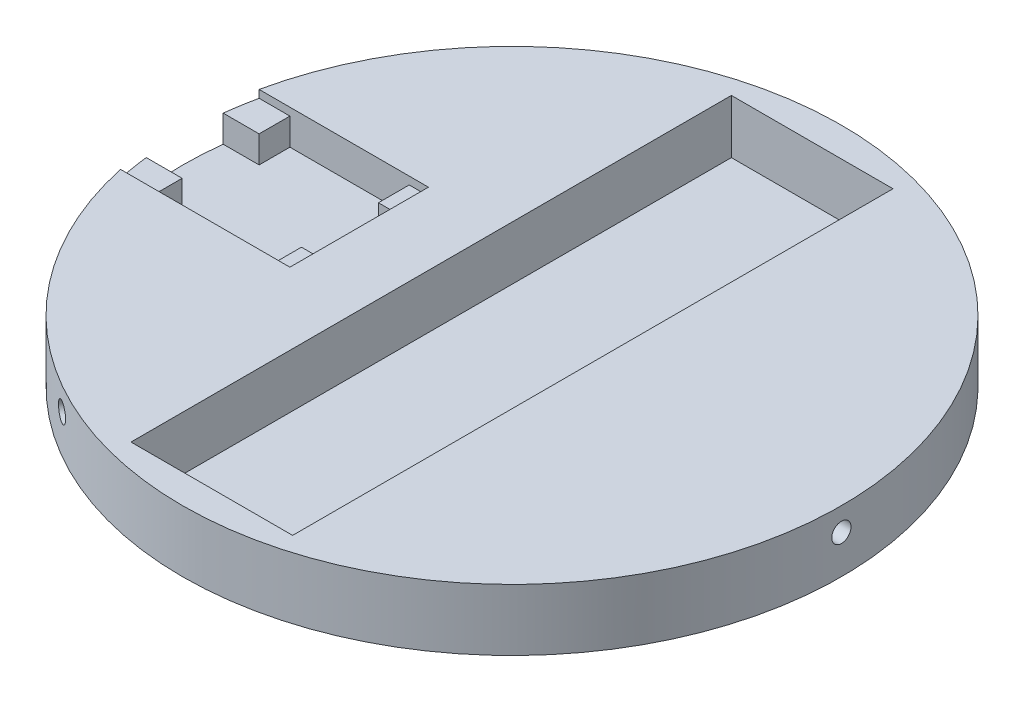
SolidWorks part; units mm, degrees
ref_plane "Front Plane" through (0, 0, 0) normal (0, 0, 1) x (1, 0, 0)
ref_plane "Top Plane" through (0, 0, 0) normal (0, 1, 0) x (1, 0, 0)
ref_plane "Right Plane" through (0, 0, 0) normal (1, 0, 0) x (0, 0, -1)
sketch "Sketch1" plane through (0, 0, 0) normal (0, 1, 0) x (1, 0, 0)
  line L1 (-10.5, -41.5024) -> (10.5, -41.5024) construction
  line L2 (-10.5, -41.5024) -> (-10.5, 41.5024)
  line L3 (-10.5, 41.5024) -> (10.5, 41.5024) construction
  line L4 (10.5, -41.5024) -> (10.5, 41.5024)
  line L5 (-10.5, -41.5024) -> (10.5, 41.5024) construction
  line L6 (-10.5, 41.5024) -> (10.5, -41.5024) construction
  circle A0 centre (0, 0) radius 42.81
  dimension "D1" = 85.62
  dimension "D2" = 21
extrude "Boss-Extrude1" add sketch "Sketch1" against normal blind 1 contours L2 A0 | L4 A0 L2 | L4 A0 region at (-23.9618, 0, 0) region at (0, 0, 0) region at (23.9618, 0, 0)
extrude "Boss-Extrude2" add sketch "Sketch1<3>" along normal blind 7 contours L4 A0 | L2 A0 region at (-23.9618, 0, 0) region at (23.9618, 0, 0)
sketch "Sketch1<3>" plane through (0, 0, 0) normal (0, 1, 0) x (1, 0, 0) same geometry as "Sketch1"
sketch "Sketch2" plane through (0, 7, 0) normal (0, 1, 0) x (1, 0, 0)
  line L0 (0, 0) -> (-42.81, 0) construction
  line L1 (-10.5, -41.5024) -> (-10.5, 41.5024) construction
  line L2 (-41.8533, 9) -> (-19.8533, 9)
  line L3 (-41.8533, 9) -> (-41.8533, -9) construction
  line L4 (-41.8533, -9) -> (-19.8533, -9)
  line L5 (-19.8533, 9) -> (-19.8533, -9)
  line L6 (-41.8533, 9) -> (-19.8533, -9) construction
  line L7 (-41.8533, -9) -> (-19.8533, 9) construction
  line L8 (-42.517, 5) -> (-37.8533, 5)
  line L9 (-37.8533, 5) -> (-37.8533, 9)
  line L10 (-22.3533, 9) -> (-22.3533, 5)
  line L11 (-22.3533, 5) -> (-19.8533, 5)
  line L12 (-22.3533, -5) -> (-19.8533, -5)
  line L13 (-22.3533, -9) -> (-22.3533, -5)
  line L14 (-37.8533, -5) -> (-37.8533, -9)
  line L15 (-42.517, -5) -> (-37.8533, -5)
  line L16 (-10.5, -41.5024) -> (-10.5, 41.5024)
  arc A0 (-10.5, 41.5024) -> (-10.5, -41.5024) centre (0, 0) ccw construction
  arc A1 (-10.5, 41.5024) -> (-10.5, -41.5024) centre (0, 0) ccw
  point P6 (-30.8533, 0)
  arc M11 (-10.5, 41.5024) -> (-10.5, -41.5024) centre (0, 0) ccw
  dimension "D1" = 18
  dimension "D2" = 22
  dimension "D3" = 4
  dimension "D4" = 2.5
  dimension "D5" = 4
extrude "Cut-Extrude1" cut sketch "Sketch2" against normal blind 1 contours L15 L4 L14 M11 | L8 L9 L2 M11 | L10 L11 L5 L2 | L13 L4 L5 L12 region at (-40.0397, 7, -6.9493) region at (-21.1033, 7, -7) region at (-40.0397, 7, 6.9493) region at (-21.1033, 7, 7)
extrude "Cut-Extrude2" cut sketch "Sketch2<3>" against normal blind 4.5 contours L15 L14 L4 L13 L12 L5 L11 L10 L2 L9 L8 M11 region at (-30.8681, 7, 0)
sketch "Sketch2<3>" plane through (0, 7, 0) normal (0, 1, 0) x (1, 0, 0) same geometry as "Sketch2"
sketch "Sketch3" plane through (0, 0, 0) normal (0, 1, 0) x (1, 0, 0)
  line L0 (10.5, -41.5024) -> (10.5, 41.5024) construction
  line L1 (-10.5, 39) -> (10.5, 39)
  line L2 (-10.5, 39) -> (-10.5, -39)
  line L3 (-10.5, -39) -> (10.5, -39)
  line L4 (10.5, 39) -> (10.5, -39)
  line L5 (-10.5, 39) -> (10.5, -39) construction
  line L6 (-10.5, -39) -> (10.5, 39) construction
  line L9 (-10.5, 41.5024) -> (-10.5, -41.5024)
  line L10 (10.5, -41.5024) -> (10.5, 41.5024)
  line L11 (-10.5, 41.5024) -> (-10.5, -41.5024)
  line L12 (10.5, -41.5024) -> (10.5, 41.5024)
  arc A2 (10.5, 41.5024) -> (-10.5, 41.5024) centre (0, 0) ccw
  arc A3 (-10.5, -41.5024) -> (10.5, -41.5024) centre (0, 0) ccw
  arc A4 (10.5, 41.5024) -> (-10.5, 41.5024) centre (0, 0) ccw
  arc A5 (-10.5, -41.5024) -> (10.5, -41.5024) centre (0, 0) ccw
  point P0 (0, 0)
  arc M9 (10.5, 41.5024) -> (-10.5, 41.5024) centre (0, 0) ccw
  line M10 (-10.5, 41.5024) -> (-10.5, -41.5024)
  arc M11 (-10.5, -41.5024) -> (10.5, -41.5024) centre (0, 0) ccw
  line M12 (10.5, -41.5024) -> (10.5, 41.5024)
  dimension "D1" = 78
  dimension "D2" = 0
extrude "Boss-Extrude3" add sketch "Sketch3" along normal blind 7 contours L1 M10 M12 M9 | L3 M10 M11 M12 region at (0, 0, -40.7108) region at (0, 0, 40.7108)
ref_plane "HoleHeight" through (0, 4, 0) normal (0, -1, 0) x (-1, 0, 0)
ref_plane "Plane2" through (42.81, 0, 0) normal (1, 0, 0) x (0, 0, -1)
sketch "Sketch4" plane through (42.81, 0, 0) normal (1, 0, 0) x (0, 0, -1)
  line L0 (-46.926, 4) -> (46.926, 4) construction
  circle A0 centre (0, 4) radius 1.25
  dimension "D1" = 2.5
extrude "Cut-Extrude3" cut sketch "Sketch4" against normal blind 11
pattern_circular "CirPattern1" count 3 every 120 about axis through (0, 7, 0) along (0, 1, 0) of "Cut-Extrude3"
